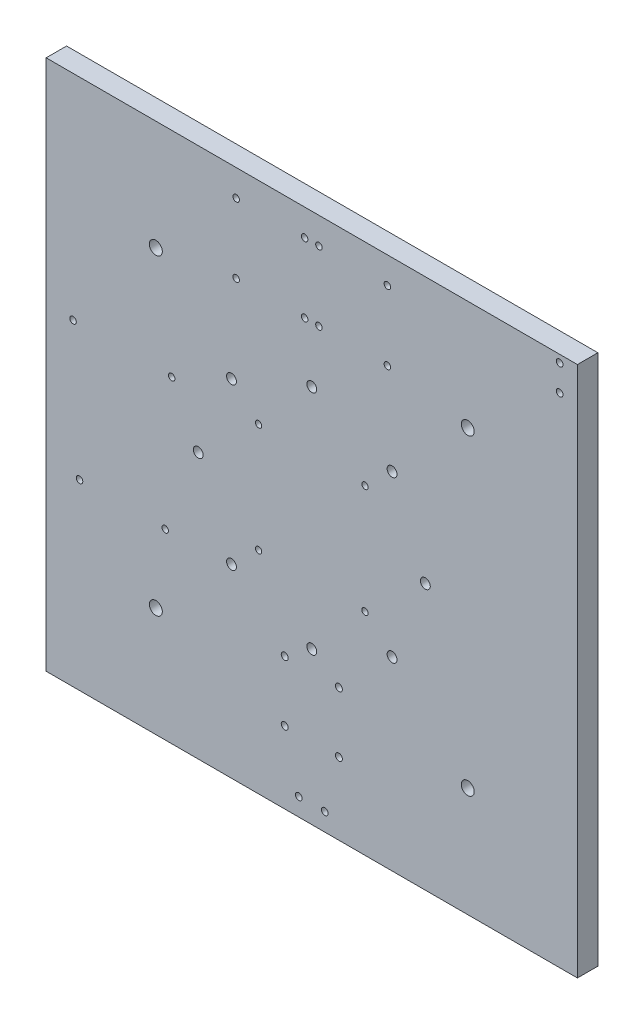
SolidWorks part; units mm, degrees
ref_plane "Front Plane" through (0, 0, 0) normal (0, 0, 1) x (1, 0, 0)
ref_plane "Top Plane" through (0, 0, 0) normal (0, 1, 0) x (1, 0, 0)
ref_plane "Right Plane" through (0, 0, 0) normal (1, 0, 0) x (0, 0, -1)
sketch "Sketch1" plane through (0, 0, 0) normal (0, 0, 1) x (1, 0, 0)
  line L0 (-130, 130) -> (130, 130)
  line L1 (130, 130) -> (130, -130)
  line L2 (130, -130) -> (-130, -130)
  line L3 (-130, -130) -> (-130, 130)
  line L4 (-120, 33.6598) -> (-120, -33.6505)
  line L5 (-29, 8) -> (-29, -8)
  line L6 (-29, 8) -> (-26.035, 8)
  line L7 (-26.035, 8) -> (-26.035, -8)
  line L8 (32.385, 33.02) -> (-32.385, 33.02)
  line L9 (-26.035, -8) -> (-29, -8)
  line L10 (-32.385, 33.02) -> (-32.385, -33.02)
  line L11 (-32.385, -33.02) -> (32.385, -33.02)
  line L12 (32.385, -33.02) -> (32.385, 33.02)
  line L13 (-107.2982, -46.3523) -> (-77.9253, -46.3523)
  line L14 (-113.65, 40.0098) -> (-71.5759, 40.0098)
  line L15 (-79.4148, 40.0098) -> (-79.4148, 22.9992)
  line L16 (-65.2259, -33.6529) -> (-65.2259, 33.6598)
  line L17 (-79.4148, 22.9992) -> (-94.8974, 22.9992)
  line L18 (-40, 120) -> (40, 120)
  line L19 (-94.8974, 22.9992) -> (-94.8974, 40.0098)
  line L31 (-40, 120) -> (-40, 80)
  line L32 (-40, 80) -> (40, 80)
  line L33 (40, 80) -> (40, 120)
  line L34 (-35, 100) -> (-35, 114.5)
  line L35 (-35, 114.5) -> (-29, 114.5)
  line L36 (-29, 114.5) -> (-29, 85.5)
  line L37 (-29, 85.5) -> (-35, 85.5)
  line L38 (-35, 85.5) -> (-35, 100)
  line L46 (16.75, -63) -> (16.75, -97)
  line L49 (16.75, -97) -> (-16.75, -97)
  line L50 (-16.75, -97) -> (-16.75, -63)
  line L51 (-16.75, -63) -> (16.75, -63)
  line L56 (120, 41.2) -> (120, -41.2)
  line L57 (45, 41.2) -> (45, -41.2)
  line L58 (120, 41.2) -> (45, 41.2)
  line L60 (45, -41.2) -> (120, -41.2)
  circle A0 centre (-26.035, 26.67) radius 1.55
  circle A1 centre (-26.035, -26.67) radius 1.55
  circle A2 centre (26.035, 26.67) radius 1.55
  circle A3 centre (26.035, -26.67) radius 1.55
  circle A4 centre (-116.825, 25.4027) radius 1.5875
  circle A5 centre (-113.65, -40.6352) radius 1.5875
  arc A6 (-120, -33.6505) -> (-107.2982, -46.3523) centre (-107.2982, -33.6505) ccw
  arc A7 (-77.9253, -46.3523) -> (-65.2259, -33.6529) centre (-77.9253, -33.6529) ccw
  arc A8 (-113.65, 40.0098) -> (-120, 33.6598) centre (-113.65, 33.6598) ccw
  arc A9 (-65.2259, 33.6598) -> (-71.5759, 40.0098) centre (-71.5759, 33.6598) ccw
  circle A10 centre (-68.565, 25.4048) radius 1.5875
  circle A11 centre (-37, 117) radius 1.6
  circle A12 centre (-37, 83) radius 1.6
  circle A13 centre (-3.5, 117) radius 1.6
  circle A14 centre (-3.5, 83) radius 1.6
  circle A15 centre (3.5, 117) radius 1.6
  circle A16 centre (37, 117) radius 1.6
  circle A17 centre (37, 83) radius 1.6
  circle A18 centre (3.5, 83) radius 1.6
  circle A19 centre (-13.25, -65.25) radius 1.7
  circle A20 centre (13.25, -65.25) radius 1.7
  circle A21 centre (13.25, -94.75) radius 1.7
  circle A22 centre (-13.25, -94.75) radius 1.7
  circle A23 centre (-76.33, 76.33) radius 3.175
  circle A24 centre (0, 55.575) radius 2.415
  circle A25 centre (-55.575, 0) radius 2.415
  circle A26 centre (0, -55.575) radius 2.415
  circle A27 centre (55.575, 0) radius 2.415
  circle A28 centre (-39.2975, 39.2975) radius 2.415
  circle A29 centre (39.2975, 39.2975) radius 2.415
  circle A30 centre (39.2975, -39.2975) radius 2.415
  circle A31 centre (-39.2975, -39.2975) radius 2.415
  circle A32 centre (76.33, 76.33) radius 3.175
  circle A33 centre (76.33, -76.33) radius 3.175
  circle A34 centre (-76.33, -76.33) radius 3.175
  arc A35 (-2.4144, 55.5225) -> (-37.5531, 40.9676) centre (0, 0) ccw
  arc A36 (37.5531, 40.9676) -> (2.4144, 55.5225) centre (0, 0) ccw
  arc A37 (55.5225, 2.4144) -> (40.9676, 37.5531) centre (0, 0) ccw
  arc A38 (40.9676, -37.5531) -> (55.5225, -2.4144) centre (0, 0) ccw
  arc A39 (2.4144, -55.5225) -> (37.5531, -40.9676) centre (0, 0) ccw
  arc A40 (-37.5531, -40.9676) -> (-2.4144, -55.5225) centre (0, 0) ccw
  arc A41 (-55.5225, -2.4144) -> (-40.9676, -37.5531) centre (0, 0) ccw
  arc A42 (-40.9676, 37.5531) -> (-55.5225, 2.4144) centre (0, 0) ccw
  circle A43 centre (-71.74, -40.6352) radius 1.5875
  circle A44 centre (6.35, -121.3) radius 1.651
  circle A45 centre (-6.35, -121.3) radius 1.651
  circle A46 centre (121.3, 126.35) radius 1.651
  circle A47 centre (121.3, 113.65) radius 1.651
  point P127 (127.65, 120)
  point P128 (-120, -120)
  point P129 (0, -127.65)
extrude "Boss-Extrude2" add sketch "Sketch1" along normal blind 10 contours L0 L1 L2 L3 | A32 | A33 | A23 | A34 | A10 | A43 | A5 | A4 | A25 | A28 | A24 | A31 | A26 | A30 | A27 | A29 | A1 | A3 | A2 | A0 | A22 | A21 | A20 | A19 | A45 | A44 | A46 | A47 | A17 | A16 | A18 | A14 | A15 | A13 | A11 | A12
